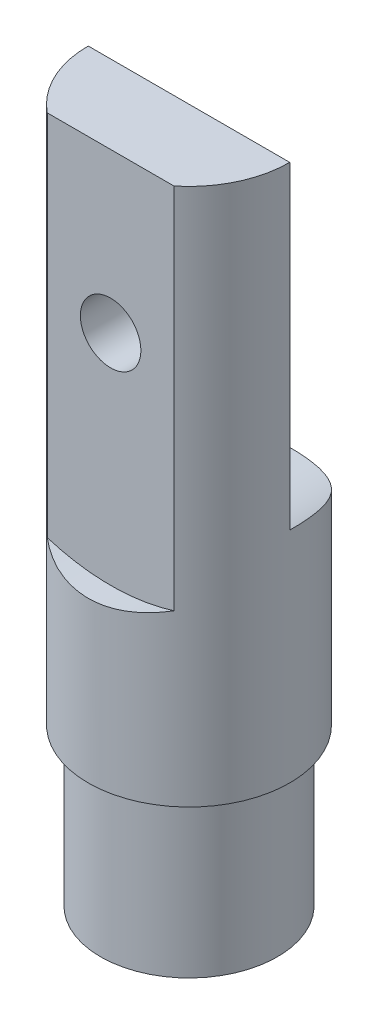
SolidWorks part; units mm, degrees
ref_plane "Front Plane" through (0, 0, 0) normal (0, 0, 1) x (1, 0, 0)
ref_plane "Top Plane" through (0, 0, 0) normal (0, 1, 0) x (1, 0, 0)
ref_plane "Right Plane" through (0, 0, 0) normal (1, 0, 0) x (0, 0, -1)
sketch "Sketch1" plane through (0, 0, 0) normal (0, 1, 0) x (1, 0, 0)
  circle A0 centre (0, 0) radius 4.5
  dimension "D1" = 9
extrude "Boss-Extrude1" add sketch "Sketch1" along normal blind 24 contours A0
sketch "Sketch2" plane through (0, 0, 0) normal (0, -1, 0) x (1, 0, 0)
  circle A0 centre (0, 0) radius 3.9
  dimension "D1" = 7.8
extrude "Boss-Extrude2" add sketch "Sketch2" along normal blind 7
sketch "Sketch4" plane through (0, 0, 0) normal (0, -1, 0) x (1, 0, 0)
  line L0 (-4.6448, 3.9) -> (4.9302, 3.9)
  line L1 (4.9302, 3.9) -> (4.9302, 6.135)
  line L2 (4.9302, 6.135) -> (-4.5584, 6.135)
  line L3 (-4.5584, 6.135) -> (-4.6448, 3.9)
  line L4 (-5.2639, -3.9) -> (5.6645, -3.9)
  line L5 (5.6645, -3.9) -> (5.6645, -4.8677)
  line L6 (5.6645, -4.8677) -> (-5.2639, -4.767)
  line L7 (-5.2639, -4.767) -> (-5.2639, -3.7879)
  circle A0 centre (0, 0) radius 3.9 construction
  circle M2 centre (0, 0) radius 4.5
extrude "Cut-Extrude3" [suppressed] cut sketch "Sketch4" against normal blind 22 contours L2 L3 L0 L1 M2 | L7 L6 L5 L4 M2 | L4 M2 | L3 L0 L1 L2
sketch "Sketch5" [suppressed] plane through (0, 0, 0) normal (1, 0, 0) x (0, 0, -1)
  line L0 (3.9, 21.5) -> (-3.9, 21.5) construction
  line L1 (5.8488, 18.5) -> (0.1, 18.5)
  line L2 (5.8488, 18.5) -> (5.8488, 14.5)
  line L3 (5.8488, 14.5) -> (0.1, 14.5)
  line L4 (0.1, 18.5) -> (0.1, 14.5)
  line L5 (-3.9, 21.5) -> (-3.9, 0) construction
  dimension "D1" = 3
  dimension "D2" = 4
  dimension "D3" = 4
extrude "Cut-Extrude4" [suppressed] cut sketch "Sketch5" against normal through all both and the other way through all
sketch "Sketch6" plane through (0, -7, 0) normal (0, -1, 0) x (1, 0, 0)
  circle A0 centre (0, 0) radius 3.95
  dimension "D1" = 7.9
sketch "Sketch7" plane through (0, -7, 0) normal (0, -1, 0) x (1, 0, 0)
  circle A0 centre (0, 0) radius 3.9
extrude "Cut-Extrude6" cut sketch "Sketch7" against normal blind 7
extrude "Boss-Extrude3" add sketch "Sketch6" against normal blind 7 contours A0
sketch "Sketch8" plane through (0, -7, 0) normal (0, -1, 0) x (1, 0, 0)
  line L1 (-3.2888, -2) -> (3.2888, -2)
  line L2 (-3.2888, -2) -> (-3.2888, 2)
  line L3 (-3.2888, 2) -> (3.2888, 2)
  line L4 (3.2888, -2) -> (3.2888, 2)
  line L5 (-3.2888, -2) -> (3.2888, 2) construction
  line L6 (-3.2888, 2) -> (3.2888, -2) construction
  line L7 (-3.5081, -2.9965) -> (3.5081, -2.9965)
  line L8 (-3.5081, -2.9965) -> (-3.5081, 2.9965)
  line L9 (-3.5081, 2.9965) -> (3.5081, 2.9965)
  line L10 (3.5081, -2.9965) -> (3.5081, 2.9965)
  line L11 (-3.5081, -2.9965) -> (3.5081, 2.9965) construction
  line L12 (-3.5081, 2.9965) -> (3.5081, -2.9965) construction
  point P0 (0, 0)
  point P6 (0, 0)
  dimension "D1" = 4
sketch "Sketch15" plane through (0, -7, 0) normal (0, -1, 0) x (1, 0, 0)
  circle A0 centre (0, 0) radius 2.5
  dimension "D1" = 5
extrude "Cut-Extrude18" cut sketch "Sketch15" against normal blind 9
sketch "Sketch9" [suppressed] plane through (0, 0, -3.9) normal (0, 0, -1) x (-1, 0, 0)
  line L0 (2.245, 0) -> (-2.245, 0) construction
  circle A0 centre (0, 19) radius 1.5
  dimension "D1" = 3
  dimension "D2" = 19
extrude "Cut-Extrude8" [suppressed] cut sketch "Sketch9" against normal blind 6
sketch "Sketch10" [suppressed] plane through (0, 0, -3.9) normal (0, 0, -1) x (-1, 0, 0)
  circle A0 centre (0, 19) radius 2
  dimension "D1" = 4
extrude "Cut-Extrude13" [suppressed] cut sketch "Sketch10" against normal blind 4
sketch "Sketch11" plane through (0, 24, 0) normal (0, 1, 0) x (1, 0, 0)
  line L0 (-4.5, 0) -> (4.5, 0)
  line L1 (-2.8284, -3.5) -> (2.8284, -3.5)
  arc A0 (4.5, 0) -> (-4.5, 0) centre (0, 0) ccw
  circle A1 centre (0, 0) radius 4.5
  arc A2 (-2.8284, -3.5) -> (2.8284, -3.5) centre (0, 0) ccw
  dimension "D2" = 3.5
  dimension "D1" = 0
extrude "Cut-Extrude14" cut sketch "Sketch11" against normal blind 8
chamfer "Chamfer1" [suppressed] distance 3 angle 55
sketch "Sketch12" plane through (0, 0, 0) normal (0, 0, -1) x (-1, 0, 0)
  circle A0 centre (0, 16.9016) radius 1.35
  dimension "D1" = 2.7
extrude "Cut-Extrude15" cut sketch "Sketch12" against normal through all
sketch "Sketch13" plane through (0, 0, 0) normal (0, 0, -1) x (-1, 0, 0)
  circle A0 centre (0, 16.9016) radius 8.426
extrude "Cut-Extrude16" cut sketch "Sketch13" along normal blind 8
sketch "Sketch14" plane through (0, 0, 3.5) normal (0, 0, 1) x (1, 0, 0)
  circle A0 centre (0, 16.5915) radius 9.4513
extrude "Cut-Extrude17" cut sketch "Sketch14" along normal blind 8
sketch "Sketch16" plane through (0, -7, 0) normal (0, -1, 0) x (1, 0, 0)
  line L1 (-2.5298, -2) -> (2.5298, -2)
  line L2 (-2.5298, -2) -> (-2.5298, 2)
  line L3 (-2.5298, 2) -> (2.5298, 2)
  line L4 (2.5298, -2) -> (2.5298, 2)
  line L5 (-2.5298, -2) -> (2.5298, 2) construction
  line L6 (-2.5298, 2) -> (2.5298, -2) construction
  line L7 (-2.8174, -2.7686) -> (2.8174, -2.7686)
  line L8 (-2.8174, -2.7686) -> (-2.8174, 2.7686)
  line L9 (-2.8174, 2.7686) -> (2.8174, 2.7686)
  line L10 (2.8174, -2.7686) -> (2.8174, 2.7686)
  line L11 (-2.8174, -2.7686) -> (2.8174, 2.7686) construction
  line L12 (-2.8174, 2.7686) -> (2.8174, -2.7686) construction
  circle A0 centre (0, 0) radius 3.95 construction
  point P0 (0, 0)
  point P6 (0, 0)
  dimension "D1" = 4
extrude "Boss-Extrude5" add sketch "Sketch16" against normal blind 11
